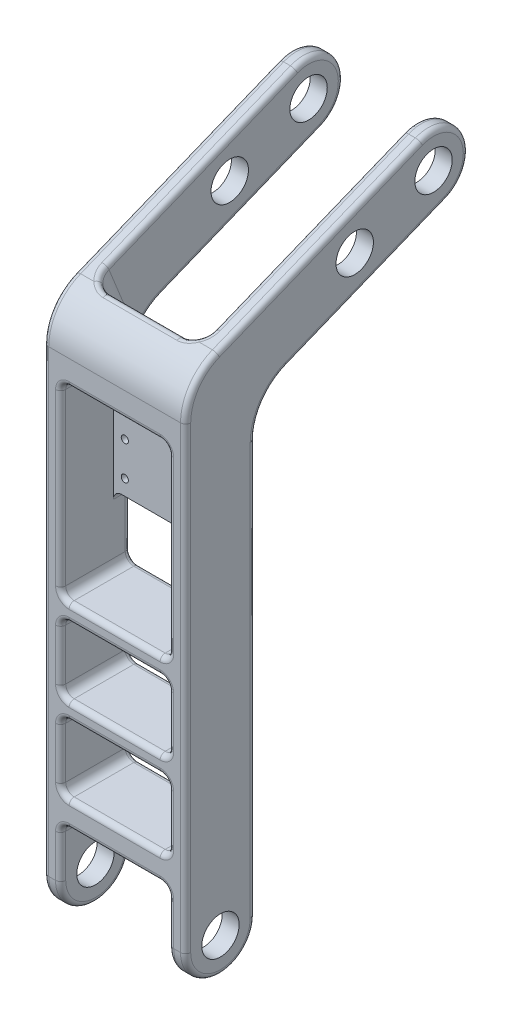
SolidWorks part; units mm, degrees
material "6061 合金"
ref_plane "前视基准面" through (0, 0, 0) normal (0, 0, 1) x (1, 0, 0)
ref_plane "上视基准面" through (0, 0, 0) normal (0, 1, 0) x (1, 0, 0)
ref_plane "右视基准面" through (0, 0, 0) normal (1, 0, 0) x (0, 0, -1)
sketch "草图1" plane through (0, 0, 0) normal (0, 0, 1) x (1, 0, 0)
  line L0 (0, 0) -> (0, 40)
  line L1 (0, 40) -> (83.5, 40)
  line L2 (83.5, 40) -> (83.5, 0)
  line L3 (83.5, 0) -> (73.5, 0)
  line L4 (73.5, 0) -> (73.5, 30)
  line L5 (73.5, 30) -> (10, 30)
  line L6 (10, 30) -> (10, 0)
  line L7 (10, 0) -> (0, 0)
  dimension "D1" = 63.5
  dimension "D2" = 10
  dimension "D3" = 30
  dimension "D4" = 10
extrude "凸台-拉伸1" add sketch "草图1" along normal blind 41
sketch "草图2" plane through (83.5, 0, 0) normal (1, 0, 0) x (0, 0, -1)
  line L0 (-41, 0) -> (0, 0)
  arc A0 (-41, 0) -> (0, 0) centre (-20.5, 0) ccw
extrude "凸台-拉伸2" add sketch "草图2" against normal blind 10
sketch "草图3" plane through (83.5, 0, 0) normal (1, 0, 0) x (0, 0, -1)
  circle A0 centre (-20.5, 0) radius 11
  dimension "D1" = 22
extrude "切除-拉伸1" cut sketch "草图3" against normal blind 10
ref_plane "基准面4" through (41.75, 0, 0) normal (1, 0, 0) x (0, 0, -1)
mirror "镜向1" about plane through (41.75, 0, 0) normal (1, 0, 0) of "凸台-拉伸2", "切除-拉伸1"
sketch "草图4" plane through (0, 40, 0) normal (0, 1, 0) x (1, 0, 0)
  line L0 (83.5, 0) -> (0, 0) construction
  line L1 (0, 0) -> (83.5, 0)
  line L2 (0, 0) -> (0, -41)
  line L3 (0, -41) -> (83.5, -41)
  line L4 (83.5, 0) -> (83.5, -41)
  line L5 (83.5, -41) -> (0, -41) construction
  line L6 (41.75, -41) -> (41.75, 5.4834) construction
extrude "凸台-拉伸3" add sketch "草图4" along normal blind 250
sketch "草图5" plane through (0, 0, 41) normal (0, 0, 1) x (1, 0, 0)
  line L0 (83.5, 0) -> (83.5, 290) construction
  line L1 (15, 45) -> (68.5, 45)
  line L2 (10, 50) -> (10, 80)
  line L3 (15, 85) -> (68.5, 85)
  line L4 (73.5, 50) -> (73.5, 80)
  line L5 (0, 290) -> (0, 0) construction
  line L6 (10, 30) -> (73.5, 30) construction
  line L23 (10, 100) -> (10, 130)
  line L24 (15, 95) -> (68.5, 95)
  line L25 (73.5, 100) -> (73.5, 130)
  line L26 (15, 135) -> (68.5, 135)
  line L27 (10, 150) -> (10, 180)
  line L28 (15, 145) -> (68.5, 145)
  line L29 (73.5, 150) -> (73.5, 180)
  line L30 (15, 185) -> (68.5, 185)
  arc A0 (68.5, 45) -> (73.5, 50) centre (68.5, 50) ccw
  arc A1 (68.5, 85) -> (73.5, 80) centre (68.5, 80) cw
  arc A2 (15, 45) -> (10, 50) centre (15, 50) cw
  arc A3 (10, 80) -> (15, 85) centre (15, 80) cw
  arc A20 (10, 130) -> (15, 135) centre (15, 130) cw
  arc A21 (15, 95) -> (10, 100) centre (15, 100) cw
  arc A22 (68.5, 95) -> (73.5, 100) centre (68.5, 100) ccw
  arc A23 (68.5, 135) -> (73.5, 130) centre (68.5, 130) cw
  arc A24 (10, 180) -> (15, 185) centre (15, 180) cw
  arc A25 (15, 145) -> (10, 150) centre (15, 150) cw
  arc A26 (68.5, 145) -> (73.5, 150) centre (68.5, 150) ccw
  arc A27 (68.5, 185) -> (73.5, 180) centre (68.5, 180) cw
  point P10 (73.5, 45)
  point P13 (73.5, 85)
  dimension "D4" = 5
  dimension "D1" = 10
  dimension "D2" = 10
  dimension "D3" = 40
  dimension "D5" = 15
  dimension "D6" = 3
extrude "切除-拉伸2" cut sketch "草图5" against normal blind 309
sketch "草图7" plane through (83.5, 0, 0) normal (1, 0, 0) x (0, 0, -1)
  line L0 (0, 262.3452) -> (112.4864, 307.7926)
  line L1 (112.4864, 307.7926) -> (97.1275, 345.8071)
  line L2 (97.1275, 345.8071) -> (-41, 290)
  line L3 (-41, 290) -> (0, 262.3452)
  line L4 (0, 0) -> (0, 290) construction
  circle A1 centre (-20.5, 0) radius 11 construction
  point P3 (104.807, 326.7999)
  dimension "D1" = 350
  dimension "D2" = 112
  dimension "D3" = 41
extrude "凸台-拉伸5" add sketch "草图7" against normal up to surface (83.5 mm away) up to face at (0, 11, 20.5)
sketch "草图8" plane through (41.75, 0, 0) normal (1, 0, 0) x (0, 0, -1)
  line L0 (0, 232.3452) -> (0, 192.3452)
  line L1 (55, 192.3452) -> (55, 210.3452)
  line L2 (0, 192.3452) -> (55, 192.3452)
  line L5 (55, 210.3452) -> (0, 232.3452)
  line L7 (0, 0) -> (0, 262.3452) construction
  dimension "D1" = 70
  dimension "D2" = 55
  dimension "D3" = 40
  dimension "D4" = 18
extrude "凸台-拉伸6" add sketch "草图8" along normal mid plane 83.5
fillet "圆角1" radius 8 1 edges at (41.75, 192.3452, -55)
sketch "草图10" plane through (83.5, 0, 0) normal (1, 0, 0) x (0, 0, -1)
  circle A0 centre (47, 200.3452) radius 5.5
  dimension "D1" = 11
extrude "切除-拉伸3" cut sketch "草图10" against normal blind 92
sketch "草图11" [suppressed] plane through (52.25, 0, 0) normal (1, 0, 0) x (0, 0, -1)
  line L0 (55, 283.0172) -> (15, 241.915)
  line L1 (55, 242.0172) -> (55, 298.0172) construction
  line L2 (15, 241.915) -> (15, 227.0172)
  line L3 (0, 227.0172) -> (40, 227.0172) construction
  line L4 (15, 227.0172) -> (64.4389, 227.0172)
  line L5 (64.4389, 227.0172) -> (55, 283.0172)
  line L6 (0, 0) -> (0, 243.0172) construction
  dimension "D1" = 15
  dimension "D2" = 15
fillet "圆角2" [suppressed] radius 5
sketch "草图13" plane through (41.75, 0, 0) normal (1, 0, 0) x (0, 0, -1)
  circle A0 centre (47, 200.3452) radius 6
  circle A1 centre (47, 200.3452) radius 5
  dimension "D1" = 10
extrude "凸台-拉伸8" [suppressed] add sketch "草图13" along normal mid plane 1
sketch "草图14" plane through (41.75, 0, 0) normal (1, 0, 0) x (0, 0, -1)
  line L0 (97.1275, 345.8071) -> (112.4864, 307.7926)
  arc A0 (97.1275, 345.8071) -> (112.4864, 307.7926) centre (104.807, 326.7999) cw
extrude "凸台-拉伸9" add sketch "草图14" against normal mid plane 83.5
sketch "草图15" plane through (83.5, 0, 0) normal (1, 0, 0) x (0, 0, -1)
  line L0 (0, 262.3452) -> (112.4864, 307.7926) construction
  circle A0 centre (104.807, 326.7999) radius 11
  circle A1 centre (58.4478, 308.0696) radius 11
  dimension "D1" = 22
  dimension "D2" = 22
  dimension "D3" = 50
  dimension "D4" = 20.5
extrude "切除-拉伸5" cut sketch "草图15" against normal mid plane 185
sketch "草图16" plane through (0, 263.5448, 106.479) normal (0, 0.9272, 0.3746) x (1, 0, 0)
  line L0 (83.5, 240.0967) -> (0, 240.0967) construction
  line L1 (10, 240.0967) -> (73.5, 240.0967)
  line L2 (10, 240.0967) -> (10, 90.0967)
  line L3 (10, 90.0967) -> (73.5, 90.0967)
  line L4 (73.5, 240.0967) -> (73.5, 90.0967)
  line L5 (83.5, 219.5967) -> (83.5, 70.6214) construction
  line L6 (0, 70.6214) -> (0, 219.5967) construction
  dimension "D1" = 10
  dimension "D2" = 10
  dimension "D3" = 150
extrude "切除-拉伸6" cut sketch "草图16" against normal blind 65
sketch "草图17" plane through (10, 0, 0) normal (1, 0, 0) x (0, 0, -1)
  circle A0 centre (58.4478, 308.0696) radius 9.5
  circle A1 centre (58.4478, 308.0696) radius 7.5
  dimension "D1" = 15
extrude "凸台-拉伸10" [suppressed] add sketch "草图17" against normal blind 4
sketch "草图18" [suppressed] plane through (73.5, 0, 0) normal (-1, 0, 0) x (0, 0, 1)
  circle A0 centre (-35.6394, 310.5764) radius 7.5
  circle A1 centre (-35.6394, 310.5764) radius 9.5
extrude "凸台-拉伸11" [suppressed] add sketch "草图18" against normal blind 4
fillet "圆角3" radius 30 3 edges at (41.75, 290, 41) (78.5, 262.3452, 0) (5, 262.3452, 0)
extrude "切除-拉伸7" cut sketch "草图8<2>" against normal mid plane 75.5
sketch "草图8<2>" plane through (41.75, 0, 0) normal (1, 0, 0) x (0, 0, -1) same geometry as "草图8"
fillet "圆角4" [suppressed] radius 8
sketch "草图19" plane through (83.5, 0, 0) normal (1, 0, 0) x (0, 0, -1)
  line L1 (0, 232.3452) -> (70.1752, 232.3452)
  line L2 (0, 232.3452) -> (0, 190.676)
  line L3 (0, 190.676) -> (70.1752, 190.676)
  line L4 (70.1752, 232.3452) -> (70.1752, 190.676)
extrude "切除-拉伸8" cut sketch "草图19" against normal blind 90.5
sketch "草图20" plane through (0, 0, 0) normal (0, 0, -1) x (-1, 0, 0)
  line L1 (-66.75, 214) -> (-16.75, 214) construction
  line L2 (-66.75, 214) -> (-66.75, 194) construction
  line L3 (-66.75, 194) -> (-16.75, 194) construction
  line L4 (-16.75, 214) -> (-16.75, 194) construction
  line L5 (-66.75, 214) -> (-16.75, 194) construction
  line L6 (-66.75, 194) -> (-16.75, 214) construction
  point P0 (-41.75, 204)
  dimension "D1" = 41.75
  dimension "D2" = 204
  dimension "D3" = 20
  dimension "D4" = 50
hole_wizard "M5 螺纹孔的螺纹孔钻头1" positions "3D草图1" profile "草图21" hole size "M5" standard "GB"
sketch3d "3D草图1"
  point P0 (66.75, 214, 0)
  point P3 (16.75, 214, 0)
  point P6 (16.75, 194, 0)
  point P9 (66.75, 194, 0)
sketch "草图21" plane through (66.75, 214, 0) normal (1, 0, 0) x (0, 1, 0)
  line L0 (0, 0) -> (0, 11.2618)
  line L1 (0, 11.2618) -> (2.1, 10)
  line L2 (2.1, 10) -> (2.1, 0)
  line L5 (2.1, 0) -> (0, 0)
  line L10 (0, 11.2618) -> (-2.1, 10) construction
  line L11 (0, -6.35) -> (0, 107.95) construction
  dimension "孔直径" = 4.2
  dimension "孔深度" = 10
  dimension "导头角度" = 118
fillet "圆角5" radius 10 2 edges at (10, 268.8985, 11.4696) (73.5, 268.8985, 11.4696)
sketch "草图22" plane through (0, 0, 41) normal (0, 0, 1) x (1, 0, 0)
  line L2 (10, 190) -> (10, 250)
  line L3 (15, 255) -> (68.5, 255)
  line L4 (73.5, 190) -> (73.5, 250)
  line L5 (10, 190) -> (10, 180)
  line L6 (10, 180) -> (10, 150) construction
  line L7 (73.5, 150) -> (73.5, 180) construction
  line L8 (10, 180) -> (73.5, 180)
  line L9 (73.5, 180) -> (73.5, 190)
  arc A0 (10, 250) -> (15, 255) centre (15, 250) cw
  arc A1 (68.5, 255) -> (73.5, 250) centre (68.5, 250) cw
  point P10 (73.5, 255)
  point P13 (73.5, 180)
  dimension "D3" = 5
  dimension "D2" = 75
extrude "切除-拉伸9" cut sketch "草图22" against normal blind 31
fillet "圆角7" radius 5 2 edges at (73.5, 30, 20.5) (10, 30, 20.5)
fillet "圆角6" radius 3 94 edges at (73.5, 12.5, 0) (73.5, -20.5, 20.5) (10, 12.5, 0) (10, -20.5, 20.5) (0, 286.5405, 35.8711) (0, 321.6937, -37.4447) (0, 334.4793, -123.8142) (0, 288.859, -65.6241) (0, 258.8857, -5.1289) (0, 121.0549, 0) (0, -20.5, 20.5) (83.5, -20.5, 20.5) (83.5, 121.0549, 0) (83.5, 258.8857, -5.1289) (83.5, 288.859, -65.6241) (83.5, 334.4793, -123.8142) (83.5, 321.6937, -37.4447) (83.5, 286.5405, 35.8711) (65.2309, 240.9132, 0) (69.9587, 246.1488, -0.2731) (73.5, 264.7741, -10.3446) (73.5, 288.859, -65.6241) (73.5, 334.4793, -123.8142) (73.5, 323.4244, -41.7283) (71.8138, 298.9599, 18.8234) (41.75, 297.2867, 22.9392) (11.6862, 298.9599, 18.8234) (10, 323.4244, -41.7283) (10, 334.4793, -123.8142) (10, 288.859, -65.6241) (10, 264.7741, -10.3446) (10.7056, 252.6354, -1.9071) (18.2691, 240.9132, 0) (11.4645, 183.5355, 0) (10, 165, 0) (11.4645, 146.4645, 0) (41.75, 145, 0) (72.0355, 146.4645, 0) (73.5, 165, 0) (72.0355, 183.5355, 0) (72.0355, 46.4645, 0) (73.5, 65, 0) (72.0355, 83.5355, 0) (41.75, 85, 0) (11.4645, 83.5355, 0) (10, 65, 0) (11.4645, 46.4645, 0) (72.0355, 96.4645, 0) (73.5, 115, 0) (72.0355, 133.5355, 0) (41.75, 135, 0) (11.4645, 133.5355, 0) (10, 115, 0) (11.4645, 96.4645, 0) (73.5, 12.5, 41) (41.75, 30, 41) (10, 12.5, 41) (0, 134.8824, 41) (83.5, 134.8824, 41) (41.75, 255, 41) (11.4645, 253.5355, 41) (10, 200, 41) (11.4645, 146.4645, 41) (41.75, 145, 41) (72.0355, 146.4645, 41) (73.5, 200, 41) (72.0355, 253.5355, 41) (72.0355, 133.5355, 41) (41.75, 135, 41) (11.4645, 133.5355, 41) (10, 115, 41) (11.4645, 96.4645, 41) (41.75, 95, 41) (72.0355, 96.4645, 41) (73.5, 115, 41) (72.0355, 83.5355, 41) (41.75, 85, 41) (11.4645, 83.5355, 41) (10, 65, 41) (11.4645, 46.4645, 41) (41.75, 45, 41) (72.0355, 46.4645, 41) (73.5, 65, 41) (41.75, 30, 0) (41.75, 240.5103, 0) (41.75, 185, 0) (41.75, 45, 0) (41.75, 95, 0) (11.4645, 28.5355, 0) (72.0355, 28.5355, 0) (72.0355, 28.5355, 41) (11.4645, 28.5355, 41)
sketch "草图23" plane through (83.5, 0, 0) normal (1, 0, 0) x (0, 0, -1)
  line L0 (-20.5, 0) -> (104.807, 326.7999) construction
  line L1 (104.807, 326.7999) -> (-20.5, 276.1726) construction
  line L2 (-20.5, 276.1726) -> (-20.5, 0) construction
  line L3 (97.1275, 345.8071) -> (-22.2382, 297.5803) construction
  dimension "D1" = 112
  dimension "D2" = 20.979
ref_plane "基准面5" through (0, 6.8529, 17.8723) normal (0, -0.358, -0.9337) x (0, 0.9337, -0.358)
